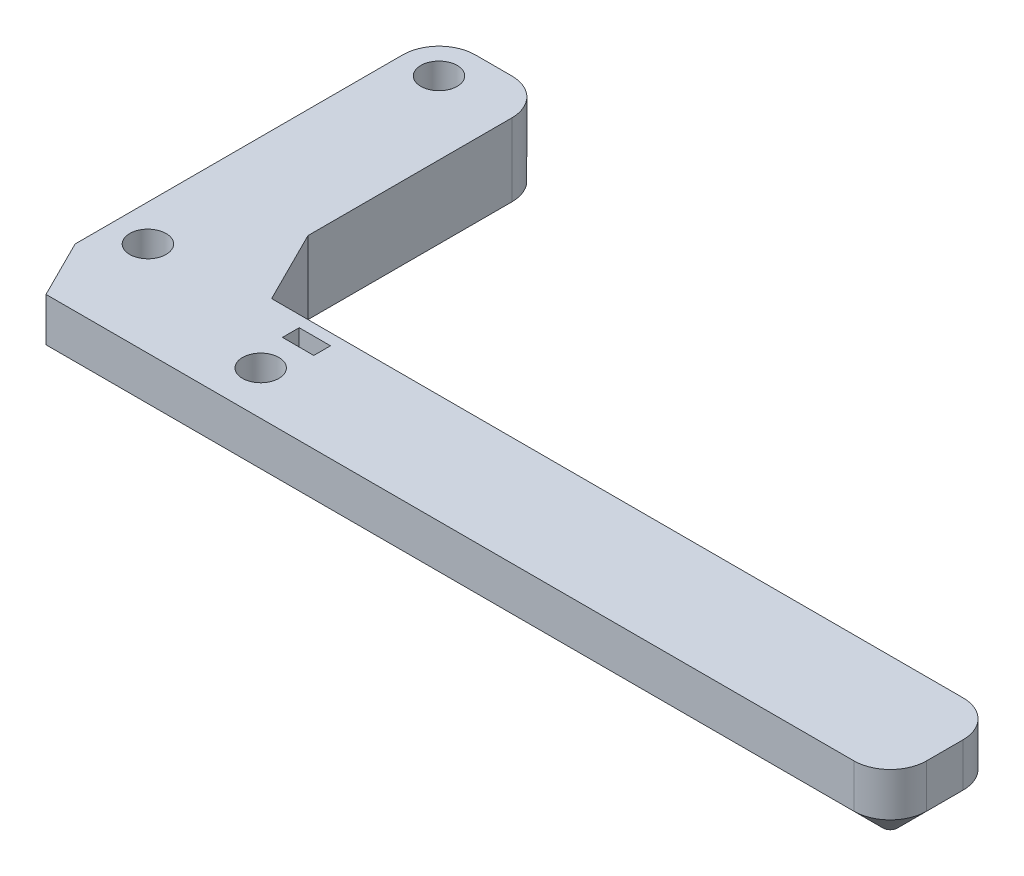
SolidWorks part; units mm, degrees
ref_plane "Front Plane" through (0, 0, 0) normal (0, 0, 1) x (1, 0, 0)
ref_plane "Top Plane" through (0, 0, 0) normal (0, 1, 0) x (1, 0, 0)
ref_plane "Right Plane" through (0, 0, 0) normal (1, 0, 0) x (0, 0, -1)
sketch "Sketch1" plane through (0, 0, 0) normal (0, 1, 0) x (1, 0, 0)
  line L0 (0, -25) -> (0, 25)
  line L1 (0, 25) -> (15, 25)
  line L2 (15, 25) -> (15, -8)
  line L4 (5, 25) -> (5, -25) construction
  line L7 (120, -18) -> (35, -18)
  line L9 (25.51, -19.72) -> (25.51, -21.72) construction
  line L10 (25.51, -21.72) -> (29.51, -21.72) construction
  line L11 (29.51, -21.72) -> (29.51, -19.72) construction
  line L12 (29.51, -19.72) -> (25.51, -19.72) construction
  line L15 (20, -18) -> (32, -18)
  line L16 (32, -18) -> (35, -18)
  line L17 (15, -8) -> (20, -18)
  line L22 (29.66, -19.57) -> (25.36, -19.57)
  line L23 (25.36, -19.57) -> (25.36, -21.87)
  line L24 (25.36, -21.87) -> (29.66, -21.87)
  line L25 (29.66, -21.87) -> (29.66, -19.57)
  line L26 (25.36, -21.87) -> (25.51, -21.72) construction
  line L27 (25.36, -19.57) -> (25.51, -19.72) construction
  line L28 (29.51, -19.72) -> (29.66, -19.57) construction
  line L29 (29.51, -21.72) -> (29.66, -21.87) construction
  line L30 (0, -25) -> (4, -33)
  line L31 (4, -33) -> (120, -33)
  line L32 (120, -33) -> (120, -18)
  circle A0 centre (5, 20) radius 2.5
  circle A1 centre (5, -20) radius 2.5
  point P3 (0, 0)
  dimension "D3" = 5
  dimension "D1" = 50
  dimension "D2" = 15
  dimension "D4" = 40
  dimension "D5" = 20
  dimension "D6" = 33
  dimension "D7" = 15
  dimension "D8" = 5
  dimension "D9" = 8
  dimension "D10" = 5
  dimension "D11" = 4
  dimension "D12" = 2
  dimension "D13" = 25.51
  dimension "D14" = 3
  dimension "D15" = 1.72
  dimension "D17" = 10
  dimension "D18" = 0.2121
  dimension "D19" = 0.2121
  dimension "D20" = 0.2121
  dimension "D21" = 0.2121
  dimension "D22" = 1.72
  dimension "D16" = 0.15
extrude "Boss-Extrude1" add sketch "Sketch1" along normal blind 10
sketch "Sketch2" plane through (0, 0, 0) normal (0, -1, 0) x (1, 0, 0)
  line L0 (10, 34.3957) -> (10, -25)
  line L2 (15, -25) -> (0, -25) construction
  line L3 (10, -25) -> (14, -25)
  line L4 (14, -25) -> (14, 34.3957)
  line L5 (14, 34.3957) -> (10, 34.3957)
  line L6 (0, -25) -> (0, 25) construction
  dimension "D1" = 10
  dimension "D2" = 4
extrude "Cut-Extrude1" cut sketch "Sketch2" against normal blind 3
fillet "Fillet3" radius 5 4 edges at (120, 5, 33) (120, 5, 18) (0, 5, -25) (15, 5, -25)
chamfer "Chamfer2" distance 4 angle 45 5 edges at (120, 0, 25.5) (64.5, 0, 33) (118.5355, 0, 31.5355) (118.5355, 0, 19.4645) (67.5, 0, 18)
sketch "Sketch3" plane through (0, 0, 0) normal (0, -1, 0) x (1, 0, 0)
  line L0 (0, -20) -> (0, 25) construction
  line L1 (10, -25) -> (5, -25) construction
  circle A0 centre (27.5, 27) radius 2.5
  dimension "D1" = 5
  dimension "D2" = 27.5
  dimension "D3" = 52
extrude "Cut-Extrude2" cut sketch "Sketch3" against normal blind 10
